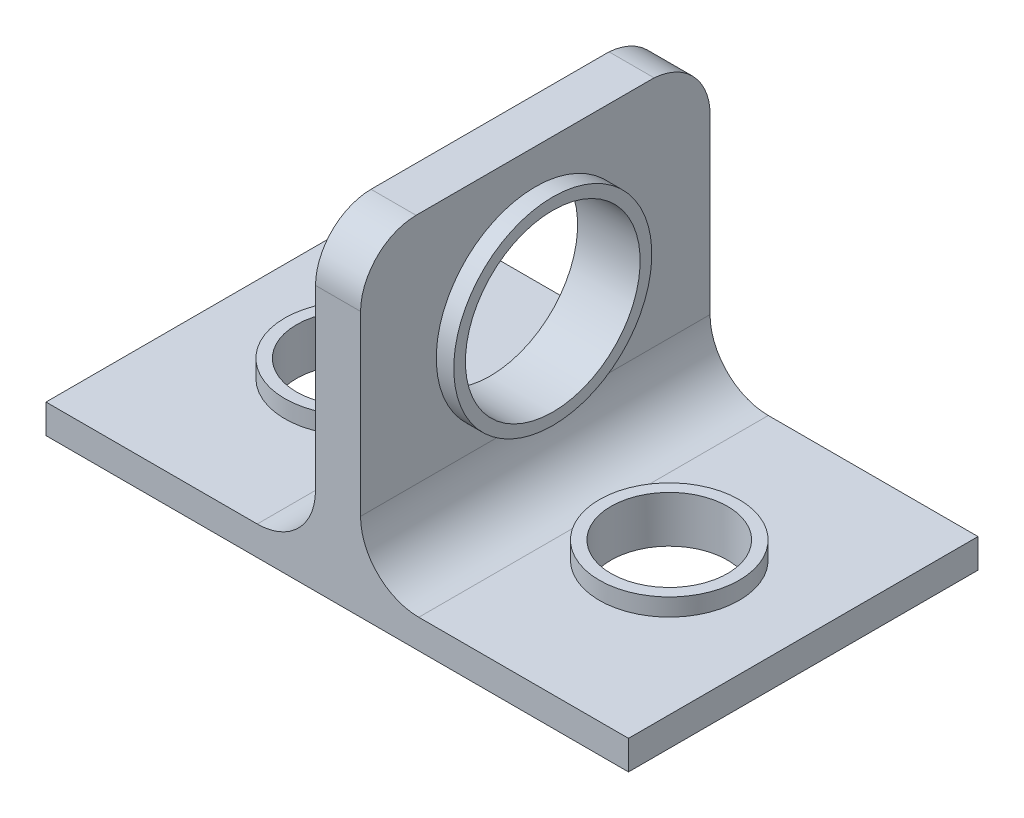
SolidWorks part; units mm, degrees
ref_plane "Front Plane" through (0, 0, 0) normal (0, 0, 1) x (1, 0, 0)
ref_plane "Top Plane" through (0, 0, 0) normal (0, 1, 0) x (1, 0, 0)
ref_plane "Right Plane" through (0, 0, 0) normal (1, 0, 0) x (0, 0, -1)
sketch "Sketch1" plane through (0, 0, 0) normal (0, 0, 1) x (1, 0, 0)
  line L25 (-47.4944, -13.6) -> (52.5056, -13.6)
  line L31 (52.5056, -13.6) -> (52.5056, -8.6)
  line L32 (52.5056, -8.6) -> (16.5056, -8.6)
  line L33 (6.5056, 41.4) -> (-1.2277, 41.4)
  line L35 (-11.2277, -8.6) -> (-47.4944, -8.6)
  line L36 (-47.4944, -8.6) -> (-47.4944, -13.6)
  line L37 (6.5056, 41.4) -> (6.5056, 1.4)
  line L40 (-1.2277, 41.4) -> (-1.2277, 1.4)
  line L41 (-24.4944, 5) -> (-24.4944, -28.3333) construction
  line L42 (29.5056, 1.4) -> (29.5056, -28.3333) construction
  line L43 (-19.8129, 16.4) -> (37.227, 16.4) construction
  arc A1 (16.5056, -8.6) -> (6.5056, 1.4) centre (16.5056, 1.4) cw
  arc A2 (-1.2277, 1.4) -> (-11.2277, -8.6) centre (-11.2277, 1.4) cw
extrude "Boss-Extrude1" add sketch "Sketch1" along normal blind 60
sketch "Sketch2" plane through (0, -8.6, 0) normal (0, 1, 0) x (1, 0, 0)
  line L0 (-53.3551, -30) -> (52.5056, -30) construction
  line L1 (52.5056, -60) -> (52.5056, 0) construction
  line L2 (-24.4944, -10.4998) -> (-24.4944, -64.4998) construction
  line L3 (29.5056, 14.2099) -> (29.5056, -64.4998) construction
  circle A0 centre (-24.4944, -30) radius 10
  circle A1 centre (-24.4944, -30) radius 12
  circle A2 centre (29.5056, -30) radius 12
  circle A3 centre (29.5056, -30) radius 10
extrude "Boss-Extrude3" add sketch "Sketch2" along normal blind 3
sketch "Sketch10" plane through (0, -8.6, 0) normal (0, 1, 0) x (1, 0, 0)
  circle A0 centre (-24.4944, -30) radius 10
  circle A1 centre (29.5056, -30) radius 10
extrude "Cut-Extrude3" cut sketch "Sketch10" against normal blind 53
sketch "Sketch11" plane through (6.5056, 0, 0) normal (1, 0, 0) x (0, 0, -1)
  line L0 (-60, 1.4) -> (-60, 41.4) construction
  line L1 (-60, 41.4) -> (0, 41.4) construction
  line L2 (0, 1.4) -> (0, 41.4) construction
  line L3 (-60, -13.6) -> (0, -13.6) construction
  circle A0 centre (-30, 18.4) radius 15
  circle A1 centre (-30, 18.4) radius 17
  circle A2 centre (-30, 18.4) radius 15
  arc A3 (-60, 31.7163) -> (-50.4697, 41.4) centre (-50.393, 31.793) cw
  arc A4 (-11.1616, 41.4) -> (0, 31.793) centre (-10.3843, 31.0157) cw
  line M2 (0, 1.4) -> (0, 41.4)
  line M3 (0, 41.4) -> (-60, 41.4)
  line M4 (-60, 41.4) -> (-60, 1.4)
  dimension "D1" = 32
extrude "Cut-Extrude4" cut sketch "Sketch11<5>" against normal blind 23 contours A0 | A3 M4 M3 | A4 M3 M2 region at (6.5056, 18.4, 30) region at (6.5056, 39.1071, 2.2929) region at (6.5056, 39.2544, 57.8544)
sketch "Sketch11<5>" plane through (6.5056, 0, 0) normal (1, 0, 0) x (0, 0, -1) same geometry as "Sketch11"
extrude "Boss-Extrude7" add sketch "Sketch11" along normal blind 3 and the other way blind 3 contours A1 A0 region at (6.5056, 18.4, 46.5192)
